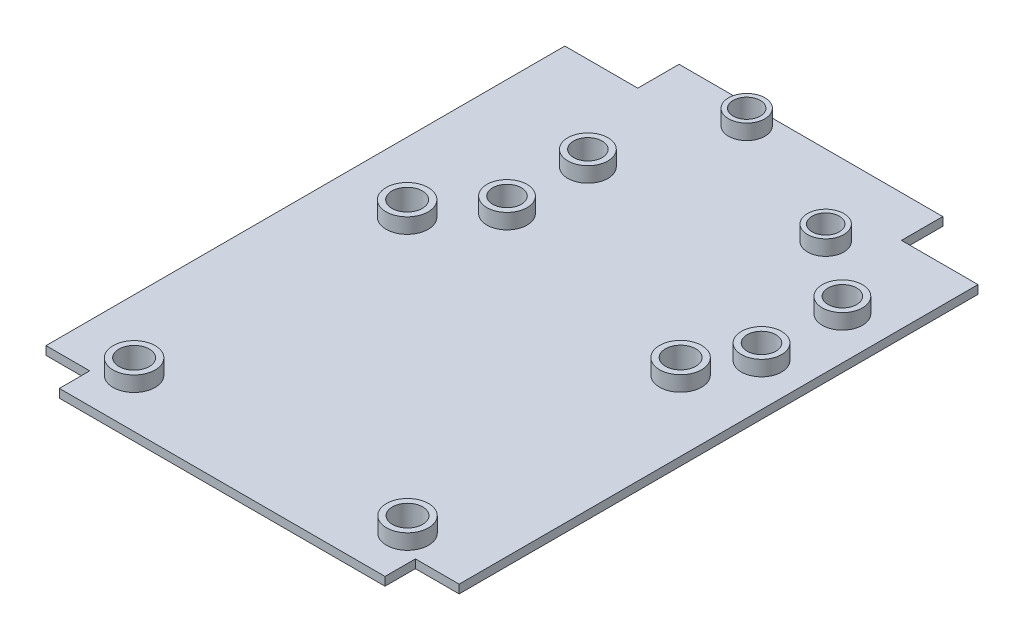
SolidWorks part; units mm, degrees
note: The reader was unsure of these and kept them because the rebuilt part matched: shared geometry of "Sketch1<4>".
ref_plane "Front Plane" through (0, 0, 0) normal (0, 0, 1) x (1, 0, 0)
ref_plane "Top Plane" through (0, 0, 0) normal (0, 1, 0) x (1, 0, 0)
ref_plane "Right Plane" through (0, 0, 0) normal (1, 0, 0) x (0, 0, -1)
sketch "Sketch1" plane through (0, 0, 0) normal (0, 1, 0) x (1, 0, 0)
  line L0 (-33.0888, -41.5944) -> (-33.0888, -47.9444)
  line L1 (43.3652, 66.8636) -> (44.1272, 66.8636)
  line L2 (-42.2328, 66.8636) -> (-42.2328, -41.5944)
  line L3 (46.8904, -41.5944) -> (44.1272, -41.5944)
  line L4 (44.1272, 66.8636) -> (44.1272, -41.5944)
  line L21 (-33.0888, -47.9444) -> (34.9832, -47.9444)
  line L22 (34.9832, -47.9444) -> (34.9832, -41.5944)
  line L23 (-42.2328, -41.5944) -> (-33.0888, -41.5944)
  line L24 (44.1272, -41.5944) -> (34.9832, -41.5944)
  line L25 (0.8349, 28.6614) -> (0.9472, -47.9444) construction
  line L26 (-37.0111, -9.1846) -> (38.6809, -9.1846) construction
  line L27 (-26.9928, 66.8636) -> (-26.9928, 75.4996)
  line L40 (-26.9928, 75.4996) -> (28.1252, 75.4996)
  line L41 (28.1252, 75.4996) -> (28.1252, 66.8636)
  line L42 (-42.2328, 66.8636) -> (-26.9928, 66.8636)
  line L43 (28.1252, 66.8636) -> (43.3652, 66.8636)
  circle A0 centre (-17.959, 47.4036) radius 3
  circle A1 centre (35.2413, 47.4036) radius 3
  circle A2 centre (35.2413, 30.4948) radius 3
  circle A3 centre (-17.959, 30.4948) radius 3
  circle A8 centre (-17.959, 47.4036) radius 4.2
  circle A9 centre (-17.959, 30.4948) radius 4.2
  circle A10 centre (35.2413, 47.4036) radius 4.2
  circle A11 centre (35.2413, 30.4948) radius 4.2
  circle A12 centre (-27.7316, 19.3954) radius 3.175
  circle A13 centre (29.4285, 19.3954) radius 3.175
  circle A14 centre (-27.6428, -37.7646) radius 3.175
  circle A15 centre (29.5073, -37.7646) radius 3.175
  circle A16 centre (-27.7316, 19.3954) radius 4.4
  circle A17 centre (-27.6428, -37.7646) radius 4.4
  circle A18 centre (29.5073, -37.7646) radius 4.4
  circle A19 centre (29.4285, 19.3954) radius 4.4
  circle A20 centre (-8.7905, 71.4328) radius 2.8448
  circle A21 centre (20.4195, 58.7328) radius 2.8448
  circle A22 centre (-8.7905, 71.4328) radius 3.8
  circle A23 centre (20.4195, 58.7328) radius 3.8
  dimension "D5" = 53.2003
  dimension "D9" = 55.118
  dimension "D3" = 9.144
  dimension "D11" = 28.575
  dimension "D21" = 29.21
  dimension "D1" = 86.36
  dimension "D2" = 108.458
  dimension "D4" = 9.144
  dimension "D6" = 53.2003
  dimension "D7" = 16.9088
  dimension "D8" = 16.9088
  dimension "D10" = 15.24
  dimension "D12" = 28.575
  dimension "D13" = 28.58
  dimension "D14" = 28.58
  dimension "D15" = 28.58
  dimension "D16" = 28.58
  dimension "D17" = 28.58
  dimension "D18" = 28.58
  dimension "D19" = 15.24
  dimension "D20" = 8.636
  dimension "D22" = 12.7
  dimension "D23" = 6.35
extrude "Boss-Extrude2" add sketch "Sketch1" along normal blind 1.778
extrude "Boss-Extrude3" add sketch "Sketch1<4>" along normal blind 4.953 contours A17 A14 | A18 A15 | A19 A13 | A16 A12 | A23 A20 | A9 A3 | A22 A21 | A8 A0 | A11 A2 | A10 A1
sketch "Sketch1<4>" plane through (0, 0, 0) normal (0, 1, 0) x (1, 0, 0) same geometry as "Sketch1"
